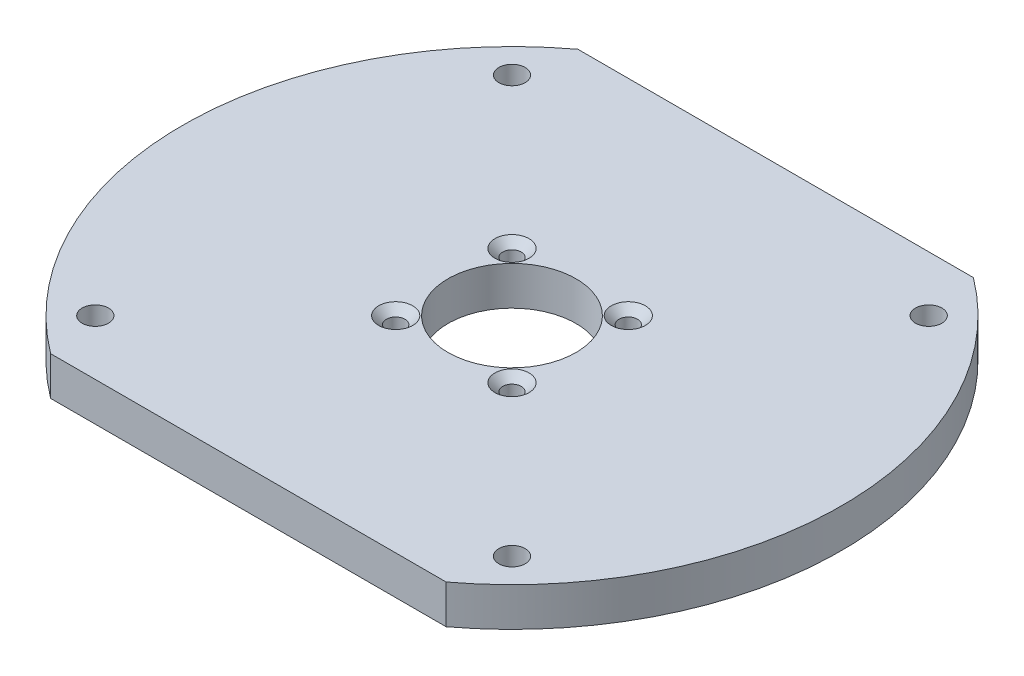
SolidWorks part; units mm, degrees
ref_plane "前基準面" through (0, 0, 0) normal (0, 0, 1) x (1, 0, 0)
ref_plane "上基準面" through (0, 0, 0) normal (0, 1, 0) x (1, 0, 0)
ref_plane "右基準面" through (0, 0, 0) normal (1, 0, 0) x (0, 0, -1)
sketch "草圖1" plane through (0, 0, 0) normal (0, 1, 0) x (1, 0, 0)
  circle A0 centre (0, 0) radius 42.5
  dimension "D1" = 85
extrude "填料-伸長1" add sketch "草圖1" along normal blind 5
sketch "草圖2" plane through (0, 5, 0) normal (0, 1, 0) x (1, 0, 0)
  circle A0 centre (0, 0) radius 8.25
  dimension "D1" = 16.5
extrude "除料-伸長1" cut sketch "草圖2" against normal through all
hole_wizard "M2 錐坑平頭螺釘的錐孔1" positions "草圖3" profile "草圖4" countersink size "M2" standard "ISO" end condition through all
sketch "草圖3" plane through (0, 5, 0) normal (0, 1, 0) x (1, 0, 0)
  line L1 (7.5, 7.5) -> (-7.5, 7.5)
  line L2 (7.5, 7.5) -> (7.5, -7.5)
  line L3 (7.5, -7.5) -> (-7.5, -7.5)
  line L4 (-7.5, 7.5) -> (-7.5, -7.5)
  line L5 (7.5, 7.5) -> (-7.5, -7.5) construction
  line L6 (7.5, -7.5) -> (-7.5, 7.5) construction
  point P0 (-7.5, 7.5)
  point P2 (7.5, 7.5)
  point P4 (7.5, -7.5)
  point P6 (-7.5, -7.5)
  dimension "D1" = 15
  dimension "D2" = 15
sketch "草圖4" plane through (-7.5, 5, -7.5) normal (1, 0, 0) x (0, 0, 1)
  line L0 (0, 0) -> (0, 5)
  line L1 (0, 5) -> (1.2, 5)
  line L2 (1.2, 5) -> (1.2, 1)
  line L3 (1.2, 1) -> (2.2, 0)
  line L5 (2.2, 0) -> (0, 0)
  line L6 (-1.2, 1) -> (-2.2, 0) construction
  line L11 (0, -6.35) -> (0, 107.95) construction
  dimension "貫穿孔直徑" = 2.4
  dimension "貫穿孔深度" = 5
  dimension "近端錐孔直徑" = 4.4
  dimension "近端錐孔角度" = 90
hole_wizard "M3 錐坑平頭螺釘的錐孔1" positions "草圖5" profile "草圖6" countersink size "M3" standard "ISO" end condition through all
sketch "草圖5" plane through (0, 0, 0) normal (0, -1, 0) x (-1, 0, 0)
  line L0 (0, 0) -> (30.052, -30.052) construction
  line L2 (0, 0) -> (0, -42.5)
  circle A0 centre (0, 0) radius 42.5 construction
  point P2 (26.8701, -26.8701)
  dimension "D1" = 38
  dimension "D2" = 45
sketch "草圖6" plane through (-26.8701, 0, 26.8701) normal (1, 0, 0) x (0, 0, -1)
  line L0 (0, 0) -> (0, 5)
  line L1 (0, 5) -> (1.7, 5)
  line L2 (1.7, 5) -> (1.7, 1.45)
  line L3 (1.7, 1.45) -> (3.15, 0)
  line L5 (3.15, 0) -> (0, 0)
  line L6 (-1.7, 1.45) -> (-3.15, 0) construction
  line L11 (0, -6.35) -> (0, 107.95) construction
  dimension "貫穿孔直徑" = 3.4
  dimension "貫穿孔深度" = 5
  dimension "近端錐孔直徑" = 6.3
  dimension "近端錐孔角度" = 90
ref_axis "基準軸1" through (0, 0, 0) along (0, 1, 0)
pattern_circular "環狀複製排列1" count 4 over 360 about axis through (0, 0, 0) along (0, 1, 0) of "M3 錐坑平頭螺釘的錐孔1"
sketch "草圖7" plane through (0, 5, 0) normal (0, 1, 0) x (1, 0, 0)
  line L0 (25.5, -34) -> (-25.5, -34)
  circle A0 centre (0, 0) radius 42.5 construction
  dimension "D1" = 34
extrude "除料-伸長2" cut sketch "草圖7" against normal through all and the other way through all
mirror "鏡射1" about plane through (0, 0, 0) normal (0, 0, 1) of "除料-伸長2"
